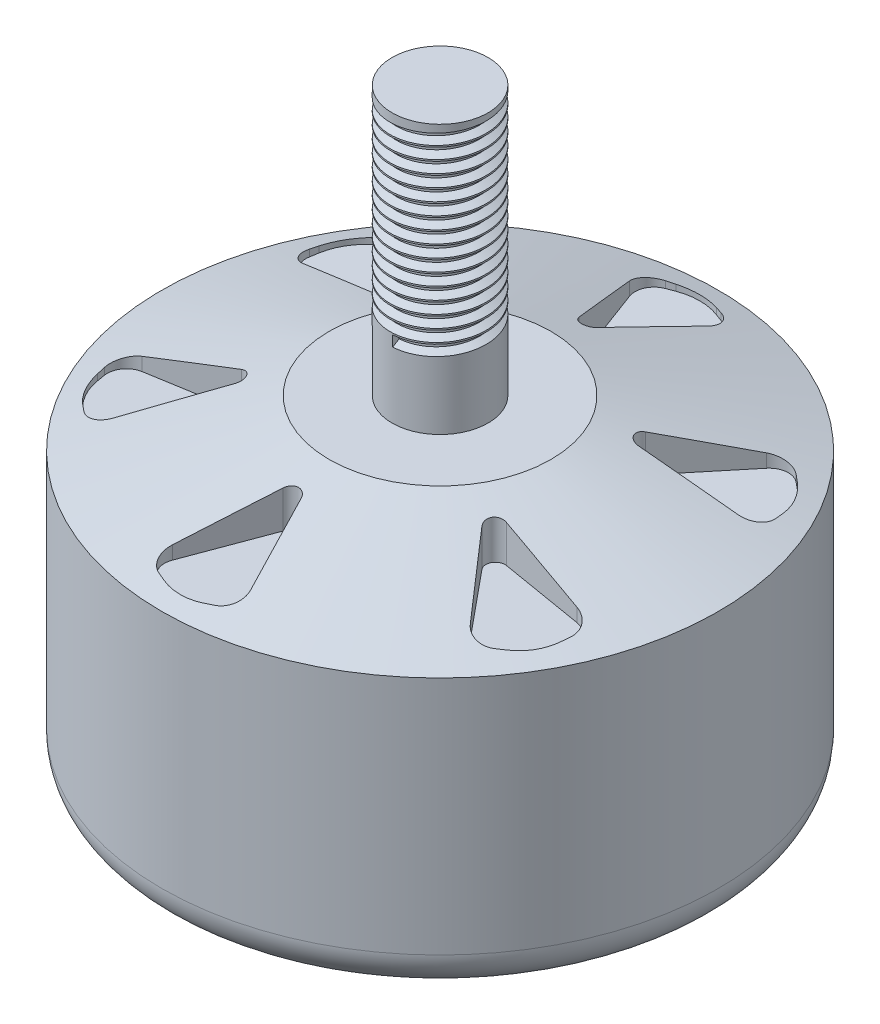
SolidWorks part; units mm, degrees
ref_plane "Front Plane" through (0, 0, 0) normal (0, 0, 1) x (1, 0, 0)
ref_plane "Top Plane" through (0, 0, 0) normal (0, 1, 0) x (1, 0, 0)
ref_plane "Right Plane" through (0, 0, 0) normal (1, 0, 0) x (0, 0, -1)
sketch "Sketch1" plane through (0, 0, 0) normal (0, 1, 0) x (1, 0, 0)
  circle A0 centre (0, 0) radius 14.5
  dimension "D1" = 29
extrude "Boss-Extrude1" add sketch "Sketch1" along normal blind 17
sketch "Sketch2" plane through (0, 17, 0) normal (0, 1, 0) x (1, 0, 0)
  circle A0 centre (0, 0) radius 2.5
  dimension "D1" = 5
extrude "Boss-Extrude2" add sketch "Sketch2" along normal blind 14 contours A0
chamfer "Chamfer1" distance 2.5 angle 74 1 edges at (0, 17, 14.5) first distance on face at (0, 17, 14.5)
fillet "Fillet1" radius 2 1 edges at (0, 0, 14.5)
sketch "Sketch4" plane through (0, 17, 0) normal (0, 1, 0) x (1, 0, 0)
  line L0 (0.4684, 7.7049) -> (2.0379, 11.907)
  line L1 (1.451, 13.1937) -> (1.0497, 13.3435)
  line L3 (-0.4684, 7.7049) -> (-2.0379, 11.907)
  line L4 (-1.451, 13.1937) -> (-1.0497, 13.3435)
  line L5 (-10.7006, 7.8534) -> (-11.031, 7.5808)
  line L6 (-12.1515, 5.3403) -> (-12.0807, 5.7627)
  line L7 (-6.9068, 3.4468) -> (-11.3307, 4.1887)
  line L8 (-6.4384, 4.2581) -> (-9.2928, 7.7183)
  line L9 (-12.1515, -5.3403) -> (-12.0807, -5.7627)
  line L10 (-10.7006, -7.8534) -> (-11.031, -7.5808)
  line L11 (-6.4384, -4.2581) -> (-9.2928, -7.7183)
  line L12 (-6.9068, -3.4468) -> (-11.3307, -4.1887)
  line L13 (-1.451, -13.1937) -> (-1.0497, -13.3435)
  line L14 (1.451, -13.1937) -> (1.0497, -13.3435)
  line L15 (0.4684, -7.7049) -> (2.0379, -11.907)
  line L16 (-0.4684, -7.7049) -> (-2.0379, -11.907)
  line L17 (10.7006, -7.8534) -> (11.031, -7.5808)
  line L18 (12.1515, -5.3403) -> (12.0807, -5.7627)
  line L19 (6.9068, -3.4468) -> (11.3307, -4.1887)
  line L20 (6.4384, -4.2581) -> (9.2928, -7.7183)
  line L21 (12.1515, 5.3403) -> (12.0807, 5.7627)
  line L22 (10.7006, 7.8534) -> (11.031, 7.5808)
  line L23 (6.4384, 4.2581) -> (9.2928, 7.7183)
  line L24 (6.9068, 3.4468) -> (11.3307, 4.1887)
  arc A0 (2.0379, 11.907) -> (1.451, 13.1937) centre (1.1011, 12.2569) ccw
  arc A1 (-2.0379, 11.907) -> (-1.451, 13.1937) centre (-1.1011, 12.2569) cw
  arc A2 (1.0497, 13.3435) -> (-1.0497, 13.3435) centre (0, 10.5332) ccw
  arc A3 (0.4684, 7.7049) -> (-0.4684, 7.7049) centre (0, 7.8798) cw
  arc A4 (-11.031, 7.5808) -> (-12.0807, 5.7627) centre (-9.122, 5.2666) ccw
  arc A5 (-9.2928, 7.7183) -> (-10.7006, 7.8534) centre (-10.0642, 7.082) ccw
  arc A6 (-11.3307, 4.1887) -> (-12.1515, 5.3403) centre (-11.1653, 5.1749) cw
  arc A7 (-6.4384, 4.2581) -> (-6.9068, 3.4468) centre (-6.8241, 3.9399) cw
  arc A8 (-12.0807, -5.7627) -> (-11.031, -7.5808) centre (-9.122, -5.2666) ccw
  arc A9 (-11.3307, -4.1887) -> (-12.1515, -5.3403) centre (-11.1653, -5.1749) ccw
  arc A10 (-9.2928, -7.7183) -> (-10.7006, -7.8534) centre (-10.0642, -7.082) cw
  arc A11 (-6.9068, -3.4468) -> (-6.4384, -4.2581) centre (-6.8241, -3.9399) cw
  arc A12 (-1.0497, -13.3435) -> (1.0497, -13.3435) centre (0, -10.5332) ccw
  arc A13 (-2.0379, -11.907) -> (-1.451, -13.1937) centre (-1.1011, -12.2569) ccw
  arc A14 (2.0379, -11.907) -> (1.451, -13.1937) centre (1.1011, -12.2569) cw
  arc A15 (-0.4684, -7.7049) -> (0.4684, -7.7049) centre (0, -7.8798) cw
  arc A16 (11.031, -7.5808) -> (12.0807, -5.7627) centre (9.122, -5.2666) ccw
  arc A17 (9.2928, -7.7183) -> (10.7006, -7.8534) centre (10.0642, -7.082) ccw
  arc A18 (11.3307, -4.1887) -> (12.1515, -5.3403) centre (11.1653, -5.1749) cw
  arc A19 (6.4384, -4.2581) -> (6.9068, -3.4468) centre (6.8241, -3.9399) cw
  arc A20 (12.0807, 5.7627) -> (11.031, 7.5808) centre (9.122, 5.2666) ccw
  arc A21 (11.3307, 4.1887) -> (12.1515, 5.3403) centre (11.1653, 5.1749) ccw
  arc A22 (9.2928, 7.7183) -> (10.7006, 7.8534) centre (10.0642, 7.082) cw
  arc A23 (6.9068, 3.4468) -> (6.4384, 4.2581) centre (6.8241, 3.9399) cw
  point P74 (0, 0)
  dimension "D1" = 1
  dimension "D2" = 3
  dimension "D3" = 0.5
  dimension "D4" = 6
extrude "Cut-Extrude1" cut sketch "Sketch4" against normal blind 2.5
thread "Thread1" pitch 0.635 method cut profile "Thread Profile1" start angle 0, offset 0, length 10, pitch 0.635, diameter 5
ref_plane "Plane1" through (-2.5, 31, 0) normal (0, 0, 1) x (-1, 0, 0)
sketch "Thread Profile1" plane through (-2.5, 31, 0) normal (0, 0, 1) x (-1, 0, 0)
  line L0 (0, 0) -> (0, 0.635) construction
  line L11 (0, 0) -> (0, 0.5556)
  line L12 (0, 0.5556) -> (-0.3437, 0.3572)
  line L13 (-0.3437, 0.3572) -> (-0.3437, 0.1984)
  line L15 (-0.3437, 0.1984) -> (0, 0)
  line L17 (-0.3437, 0.2778) -> (0, 0.2778) construction
  point P2 (0, 0)
  dimension "Pitch" = 0.635
  dimension "Profile_Angle" = 60
  dimension "Profile_Land" = 0.1588
  dimension "Profile_Height" = 0.3437
sketch "Sketch14" plane through (0, 0, 0) normal (0, -1, 0) x (1, 0, 0)
  line L0 (-2.1169, 7.7148) -> (2.1169, -7.7148) construction
  line L1 (-9.1614, -2.5139) -> (9.1614, 2.5139) construction
  circle A0 centre (-2.1169, 7.7148) radius 1.5
  circle A1 centre (2.1169, -7.7148) radius 1.5
  circle A2 centre (-9.1614, -2.5139) radius 1.5
  circle A3 centre (9.1614, 2.5139) radius 1.5
  point P9 (0, 0)
  dimension "D1" = 3
  dimension "D2" = 3
  dimension "D3" = 16
  dimension "D4" = 3
  dimension "D5" = 3
  dimension "D6" = 19
extrude "Cut-Extrude2" cut sketch "Sketch14" against normal blind 4
sketch "Sketch15" plane through (0, 0, 0) normal (0, -1, 0) x (1, 0, 0)
  circle A0 centre (0, 0) radius 3
  dimension "D1" = 6
extrude "Boss-Extrude3" add sketch "Sketch15" along normal blind 1
